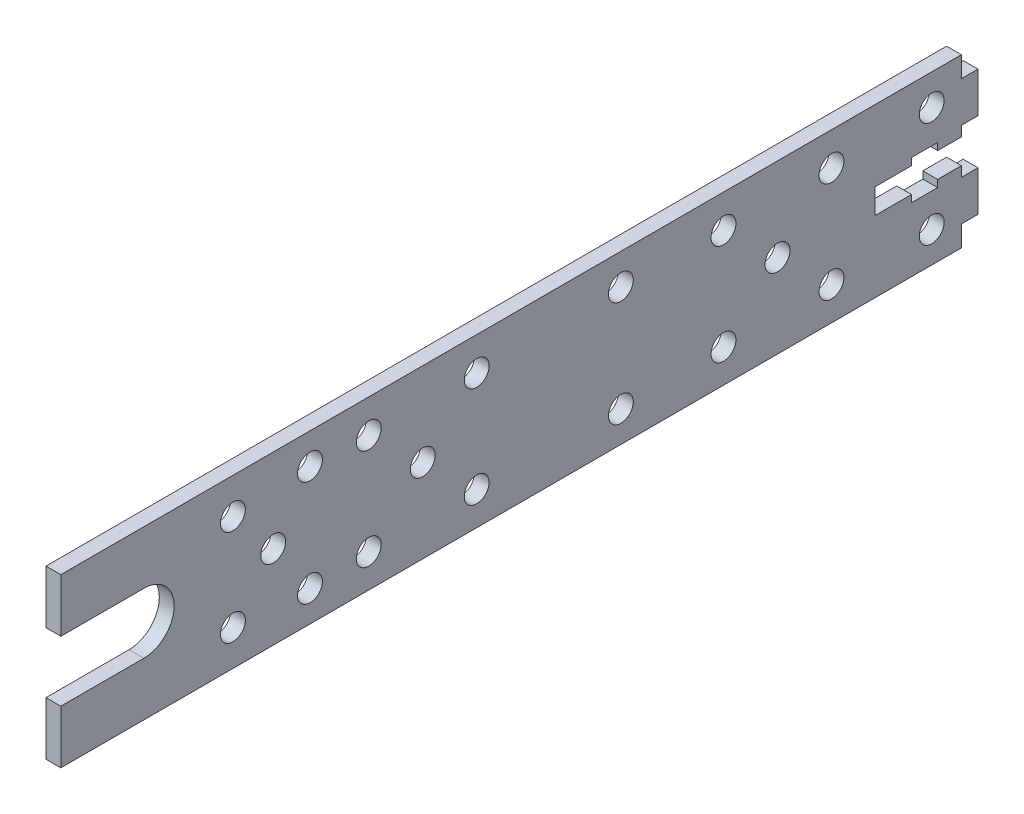
SolidWorks part; units mm, degrees
ref_plane "Front Plane" through (0, 0, 0) normal (0, 0, 1) x (1, 0, 0)
ref_plane "Top Plane" through (0, 0, 0) normal (0, 1, 0) x (1, 0, 0)
ref_plane "Right Plane" through (0, 0, 0) normal (1, 0, 0) x (0, 0, -1)
sketch "Sketch1" plane through (0, 0, 0) normal (1, 0, 0) x (0, 0, -1)
  line L0 (-98.171, 0) -> (98.171, 0) construction
  line L1 (-98.171, 17.907) -> (94.615, 17.907)
  line L2 (-98.171, 17.907) -> (-98.171, 6.477)
  line L3 (-98.171, -17.907) -> (94.615, -17.907)
  line L4 (98.171, 13.462) -> (98.171, 4.826)
  line L5 (94.615, 4.826) -> (94.615, 2.667)
  line L6 (94.615, -2.667) -> (94.615, -4.826)
  line L7 (94.615, 2.667) -> (89.535, 2.667)
  line L8 (94.615, 17.907) -> (94.615, 13.462)
  line L9 (94.615, -2.667) -> (89.535, -2.667)
  line L10 (76.073, 2.667) -> (76.073, -2.667)
  line L11 (86.741, 4.191) -> (86.741, -4.191) construction
  line L12 (-32.258, 10.795) -> (-9.144, 10.795) construction
  line L13 (83.947, 2.667) -> (76.073, 2.667)
  line L14 (89.535, 4.191) -> (83.947, 4.191)
  line L15 (89.535, 4.191) -> (89.535, 2.667)
  line L16 (89.535, -4.191) -> (83.947, -4.191)
  line L17 (83.947, 4.191) -> (83.947, 2.667)
  line L18 (66.802, 10.795) -> (43.688, 10.795) construction
  line L19 (66.802, -10.795) -> (43.688, -10.795) construction
  line L20 (83.947, -2.667) -> (76.073, -2.667)
  line L21 (89.535, -2.667) -> (89.535, -4.191)
  line L22 (83.947, -2.667) -> (83.947, -4.191)
  line L23 (98.171, -4.826) -> (98.171, -13.462)
  line L24 (98.171, 13.462) -> (94.615, 13.462)
  line L25 (98.171, 13.462) -> (98.171, 4.826)
  line L26 (98.171, 4.826) -> (94.615, 4.826)
  line L27 (-32.258, -10.795) -> (-9.144, -10.795) construction
  line L28 (98.171, 13.462) -> (94.615, 4.826) construction
  line L29 (98.171, 4.826) -> (94.615, 13.462) construction
  line L30 (-80.391, 6.477) -> (-98.171, 6.477)
  line L31 (98.171, -4.826) -> (94.615, -4.826)
  line L32 (-20.701, 10.795) -> (-20.701, -10.795) construction
  line L33 (98.171, -13.462) -> (94.615, -4.826) construction
  line L34 (98.171, -4.826) -> (94.615, -13.462) construction
  line L35 (98.171, -13.462) -> (94.615, -13.462)
  line L36 (-80.391, -6.477) -> (-98.171, -6.477)
  line L37 (-98.171, -6.477) -> (-98.171, -17.907)
  line L38 (94.615, -13.462) -> (94.615, -17.907)
  line L39 (55.245, 10.795) -> (55.245, -10.795) construction
  arc A0 (-80.391, -6.477) -> (-80.391, 6.477) centre (-80.391, 0) ccw
  circle A1 centre (-61.341, 10.287) radius 2.667
  circle A2 centre (-61.341, -10.287) radius 2.667
  circle A3 centre (-52.705, 0) radius 2.667
  circle A4 centre (-44.831, 11.303) radius 2.667
  circle A5 centre (21.717, 11.303) radius 2.667
  circle A6 centre (88.265, 11.303) radius 2.667
  circle A7 centre (88.265, -11.303) radius 2.667
  circle A8 centre (21.717, -11.303) radius 2.667
  circle A9 centre (-44.831, -11.303) radius 2.667
  circle A10 centre (-9.144, 10.795) radius 2.667
  circle A11 centre (-32.258, 10.795) radius 2.667
  circle A12 centre (66.802, 10.795) radius 2.667
  circle A13 centre (43.688, 10.795) radius 2.667
  circle A14 centre (43.688, -10.795) radius 2.667
  circle A15 centre (66.802, -10.795) radius 2.667
  circle A16 centre (-32.258, -10.795) radius 2.667
  circle A17 centre (-9.144, -10.795) radius 2.667
  circle A18 centre (-20.701, 0) radius 2.667
  circle A19 centre (55.245, 0) radius 2.667
  point P0 (0, 0)
  point P1 (86.741, 0)
  point P4 (0, 0)
  point P26 (96.393, 9.144)
  point P30 (96.393, -9.144)
  point P44 (76.073, 0)
  dimension "D11" = 12.954
  dimension "D15" = 5.334
  dimension "D26" = 17.78
  dimension "D24" = 39.37
  dimension "D2" = 192.786
  dimension "D3" = 5.334
  dimension "D4" = 18.542
  dimension "D5" = 5.588
  dimension "D6" = 8.636
  dimension "D7" = 8.382
  dimension "D8" = 3.556
  dimension "D9" = 8.636
  dimension "D10" = 9.144
  dimension "D12" = 17.78
  dimension "D13" = 11.43
  dimension "D14" = 11.43
  dimension "D16" = 7.62
  dimension "D17" = 36.83
  dimension "D18" = 150.876
  dimension "D19" = 9.906
  dimension "D20" = 6.604
  dimension "D21" = 76.454
  dimension "D22" = 143.002
  dimension "D23" = 7.112
  dimension "D25" = 115.316
extrude "Boss-Extrude1" add sketch "Sketch1" along normal mid plane 3.175 contours A0 L36 L37 L3 L6 L9 L21 L16 L22 L20 L10 L13 L17 L14 L15 L7 L5 L26 L4 L24 L8 L1 L2 L30 A16 A14 A13 A12 A11 A10 A8 A2 A1 A3 A4 A5 region at (0, 0, -1.0693)
